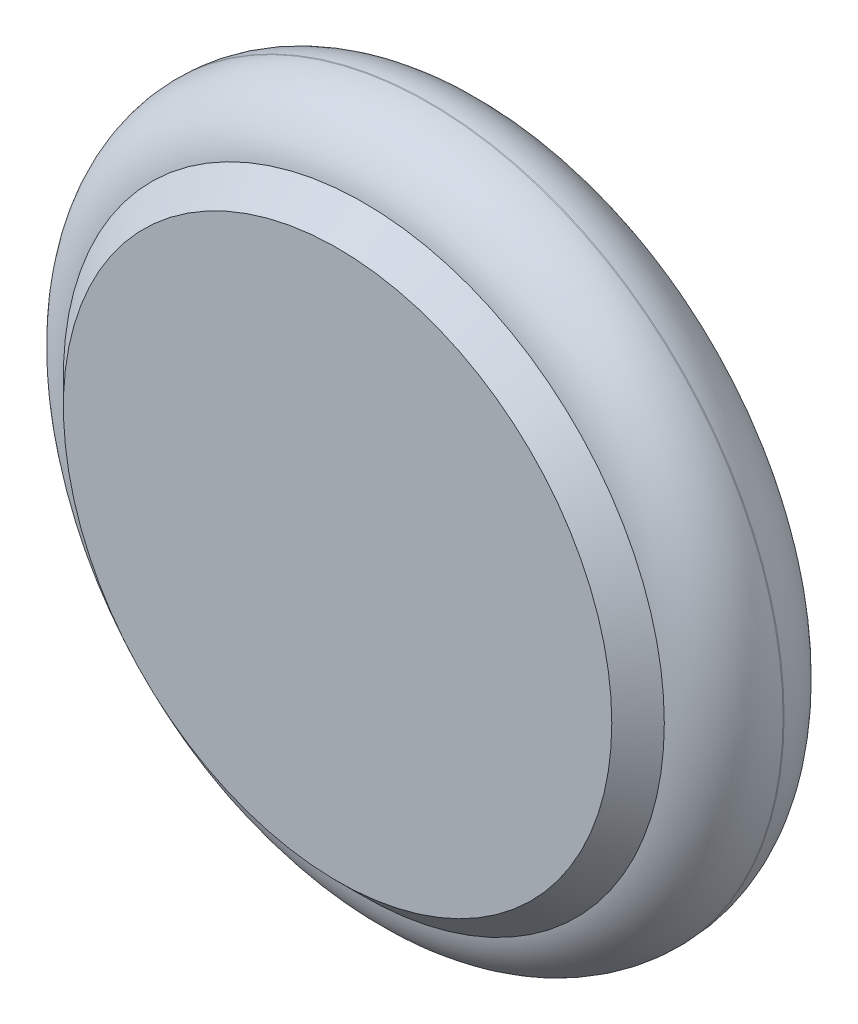
SolidWorks part; units mm, degrees
ref_plane "Front Plane" through (0, 0, 0) normal (0, 0, 1) x (1, 0, 0)
ref_plane "Top Plane" through (0, 0, 0) normal (0, 1, 0) x (1, 0, 0)
ref_plane "Right Plane" through (0, 0, 0) normal (1, 0, 0) x (0, 0, -1)
sketch "Sketch1" plane through (0, 0, 0) normal (0, 0, 1) x (1, 0, 0)
  circle A0 centre (0, 0) radius 108
  dimension "D1" = 216
extrude "Boss-Extrude1" add sketch "Sketch1" along normal blind 40
sketch "Sketch2" plane through (0, 0, 0) normal (0, 0, -1) x (-1, 0, 0)
  circle A0 centre (0, 0) radius 6.75
  dimension "D1" = 13.5
sketch "Sketch3" plane through (0, 0, 40) normal (0, 0, 1) x (1, 0, 0)
  circle A0 centre (0, 0) radius 91.5182
extrude "Boss-Extrude3" add sketch "Sketch3" along normal blind 8
chamfer "Chamfer1" distance 8 angle 45 1 edges at (91.5182, 0, 48)
fillet "Fillet2" radius 20 2 edges at (108, 0, 0) (108, 0, 40)
sketch "Sketch5" plane through (0, 0, 0) normal (0, 0, -1) x (-1, 0, 0)
  circle A1 centre (0, 0) radius 20
extrude "Boss-Extrude4" add sketch "Sketch5" along normal blind 2
chamfer "Chamfer2" distance 4 angle 45 1 edges at (-20, 0, -2)
sketch "Sketch6" plane through (0, 0, -2) normal (0, 0, -1) x (-1, 0, 0)
  circle A0 centre (0, 0) radius 7.3443
